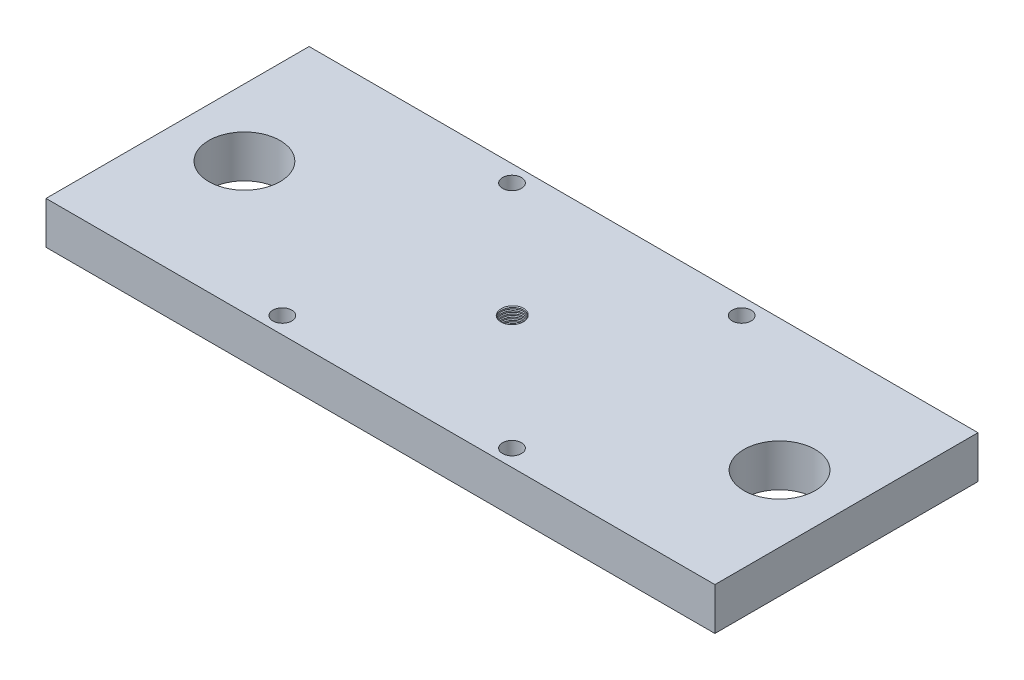
SolidWorks part; units mm, degrees
ref_plane "Front Plane" through (0, 0, 0) normal (0, 0, 1) x (1, 0, 0)
ref_plane "Top Plane" through (0, 0, 0) normal (0, 1, 0) x (1, 0, 0)
ref_plane "Right Plane" through (0, 0, 0) normal (1, 0, 0) x (0, 0, -1)
sketch "Sketch1" plane through (0, 0, 0) normal (0, 1, 0) x (1, 0, 0)
  line L1 (-150, -59) -> (150, -59)
  line L2 (-150, -59) -> (-150, 59)
  line L3 (-150, 59) -> (150, 59)
  line L4 (150, -59) -> (150, 59)
  line L5 (-150, -59) -> (150, 59) construction
  line L6 (-150, 59) -> (150, -59) construction
  circle A0 centre (0, 0) radius 5
  point P1 (0, 0)
  dimension "D3" = 10
  dimension "D1" = 118
  dimension "D2" = 300
extrude "Boss-Extrude1" add sketch "Sketch1" along normal blind 19
sketch "Sketch2" plane through (0, 19, 0) normal (0, 1, 0) x (1, 0, 0)
  circle A0 centre (0, 0) radius 5
  dimension "D1" = 10
sketch "Sketch4" plane through (0, 19, 0) normal (0, 1, 0) x (1, 0, 0)
  line L0 (-150, 59) -> (-150, -59) construction
  line L1 (150, -59) -> (150, 59) construction
  circle A0 centre (-120, 0) radius 16
  circle A1 centre (120, 0) radius 16
  dimension "D3" = 32
  dimension "D1" = 30
  dimension "D2" = 30
extrude "Cut-Extrude1" cut sketch "Sketch4" against normal through all
sketch "Sketch6" plane through (0, 0, 0) normal (0, 1, 0) x (1, 0, 0)
  line L0 (-150, 59) -> (-150, -59) construction
  line L1 (-145.4112, 0) -> (187.1629, 0) construction
  circle A0 centre (-51.5, 51.5) radius 4.25
  circle A1 centre (51.5, 51.5) radius 4.25
  circle A2 centre (51.5, -51.5) radius 4.25
  circle A3 centre (-51.5, -51.5) radius 4.25
  point P16 (0, 0)
  dimension "D1" = 8.5
  dimension "D2" = 51.5
  dimension "D3" = 98.5
  dimension "D4" = 4
extrude "Cut-Extrude11" cut sketch "Sketch6" along direction (0, -1, 0) on the side against the normal blind 9 and the other way blind 19
sketch "Sketch7" plane through (0, 0, 0) normal (0, 1, 0) x (1, 0, 0)
  circle A0 centre (0, 0) radius 5
  circle A1 centre (0, 0) radius 5 construction
curve "Helix/Spiral1" pitch 1.25 height 20.3125 turns 16.25
sketch "Sketch8" plane through (0, 0, 0) normal (1, 0, 0) x (0, 0, -1)
  line L0 (5, 20.625) -> (5, 20)
  line L1 (5, 20) -> (5.5, 20.3125)
  line L2 (5.5, 20.3125) -> (5, 20.625)
  spline S1 degree 3 poles (0, 0) (0.6503, 0.0259) (1.9651, 0.0782) (3.6271, 0.1562) (4.7398, 0.2344) (5.1301, 0.3125) (4.7397, 0.3906) (3.6276, 0.4687) (1.9632, 0.5469) (0, 0.625) (-1.9632, 0.7031) (-3.6276, 0.7812) (-4.7397, 0.8594) (-5.1302, 0.9375) (-4.7397, 1.0156) (-3.6276, 1.0937) (-1.9632, 1.1719) (0, 1.25) (1.9632, 1.3281) (3.6276, 1.4062) (4.7397, 1.4844) (5.1302, 1.5625) (4.7397, 1.6406) (3.6276, 1.7188) (1.9632, 1.7969) (0, 1.875) (-1.9632, 1.9531) (-3.6276, 2.0313) (-4.7397, 2.1094) (-5.1302, 2.1875) (-4.7397, 2.2656) (-3.6276, 2.3438) (-1.9632, 2.4219) (0, 2.5) (1.9632, 2.5781) (3.6276, 2.6563) (4.7397, 2.7344) (5.1302, 2.8125) (4.7397, 2.8906) (3.6276, 2.9688) (1.9632, 3.0469) (0, 3.125) (-1.9632, 3.2031) (-3.6276, 3.2813) (-4.7397, 3.3594) (-5.1302, 3.4375) (-4.7397, 3.5156) (-3.6276, 3.5938) (-1.9632, 3.6719) (0, 3.75) (1.9632, 3.8281) (3.6276, 3.9063) (4.7397, 3.9844) (5.1302, 4.0625) (4.7397, 4.1406) (3.6276, 4.2188) (1.9632, 4.2969) (0, 4.375) (-1.9632, 4.4531) (-3.6276, 4.5313) (-4.7397, 4.6094) (-5.1302, 4.6875) (-4.7397, 4.7656) (-3.6276, 4.8438) (-1.9632, 4.9219) (0, 5) (1.9632, 5.0781) (3.6276, 5.1563) (4.7397, 5.2344) (5.1302, 5.3125) (4.7397, 5.3906) (3.6276, 5.4688) (1.9632, 5.5469) (0, 5.625) (-1.9632, 5.7031) (-3.6276, 5.7813) (-4.7397, 5.8594) (-5.1302, 5.9375) (-4.7397, 6.0156) (-3.6276, 6.0938) (-1.9632, 6.1719) (0, 6.25) (1.9632, 6.3281) (3.6276, 6.4063) (4.7397, 6.4844) (5.1302, 6.5625) (4.7397, 6.6406) (3.6276, 6.7188) (1.9632, 6.7969) (0, 6.875) (-1.9632, 6.9531) (-3.6276, 7.0313) (-4.7397, 7.1094) (-5.1302, 7.1875) (-4.7397, 7.2656) (-3.6276, 7.3438) (-1.9632, 7.4219) (0, 7.5) (1.9632, 7.5781) (3.6276, 7.6563) (4.7397, 7.7344) (5.1302, 7.8125) (4.7397, 7.8906) (3.6276, 7.9688) (1.9632, 8.0469) (0, 8.125) (-1.9632, 8.2031) (-3.6276, 8.2813) (-4.7397, 8.3594) (-5.1302, 8.4375) (-4.7397, 8.5156) (-3.6276, 8.5938) (-1.9632, 8.6719) (0, 8.75) (1.9632, 8.8281) (3.6276, 8.9063) (4.7397, 8.9844) (5.1302, 9.0625) (4.7397, 9.1406) (3.6276, 9.2188) (1.9632, 9.2969) (0, 9.375) (-1.9632, 9.4531) (-3.6276, 9.5313) (-4.7397, 9.6094) (-5.1302, 9.6875) (-4.7397, 9.7656) (-3.6276, 9.8438) (-1.9632, 9.9219) (0, 10) (1.9632, 10.0781) (3.6276, 10.1563) (4.7397, 10.2344) (5.1302, 10.3125) (4.7397, 10.3906) (3.6276, 10.4688) (1.9632, 10.5469) (0, 10.625) (-1.9632, 10.7031) (-3.6276, 10.7813) (-4.7397, 10.8594) (-5.1302, 10.9375) (-4.7397, 11.0156) (-3.6276, 11.0938) (-1.9632, 11.1719) (0, 11.25) (1.9632, 11.3281) (3.6276, 11.4063) (4.7397, 11.4844) (5.1302, 11.5625) (4.7397, 11.6406) (3.6276, 11.7188) (1.9632, 11.7969) (0, 11.875) (-1.9632, 11.9531) (-3.6276, 12.0313) (-4.7397, 12.1094) (-5.1302, 12.1875) (-4.7397, 12.2656) (-3.6276, 12.3438) (-1.9632, 12.4219) (0, 12.5) (1.9632, 12.5781) (3.6276, 12.6563) (4.7397, 12.7344) (5.1302, 12.8125) (4.7397, 12.8906) (3.6276, 12.9688) (1.9632, 13.0469) (0, 13.125) (-1.9632, 13.2031) (-3.6276, 13.2813) (-4.7397, 13.3594) (-5.1302, 13.4375) (-4.7397, 13.5156) (-3.6276, 13.5938) (-1.9632, 13.6719) (0, 13.75) (1.9632, 13.8281) (3.6276, 13.9063) (4.7397, 13.9844) (5.1302, 14.0625) (4.7397, 14.1406) (3.6276, 14.2188) (1.9632, 14.2969) (0, 14.375) (-1.9632, 14.4531) (-3.6276, 14.5313) (-4.7397, 14.6094) (-5.1302, 14.6875) (-4.7397, 14.7656) (-3.6276, 14.8438) (-1.9632, 14.9219) (0, 15) (1.9632, 15.0781) (3.6276, 15.1563) (4.7397, 15.2344) (5.1302, 15.3125) (4.7397, 15.3906) (3.6276, 15.4688) (1.9632, 15.5469) (0, 15.625) (-1.9632, 15.7031) (-3.6276, 15.7813) (-4.7397, 15.8594) (-5.1302, 15.9375) (-4.7397, 16.0156) (-3.6276, 16.0938) (-1.9632, 16.1719) (0, 16.25) (1.9632, 16.3281) (3.6276, 16.4062) (4.7397, 16.4844) (5.1302, 16.5625) (4.7397, 16.6406) (3.6276, 16.7187) (1.9632, 16.7969) (0, 16.875) (-1.9632, 16.9531) (-3.6276, 17.0312) (-4.7397, 17.1094) (-5.1302, 17.1875) (-4.7397, 17.2656) (-3.6276, 17.3437) (-1.9632, 17.4219) (0, 17.5) (1.9632, 17.5781) (3.6276, 17.6562) (4.7397, 17.7344) (5.1302, 17.8125) (4.7397, 17.8906) (3.6276, 17.9687) (1.9632, 18.0469) (0, 18.125) (-1.9632, 18.2031) (-3.6276, 18.2812) (-4.7397, 18.3594) (-5.1302, 18.4375) (-4.7397, 18.5156) (-3.6276, 18.5937) (-1.9632, 18.6719) (0, 18.75) (1.9632, 18.8281) (3.6276, 18.9062) (4.7397, 18.9844) (5.1302, 19.0625) (4.7397, 19.1406) (3.6276, 19.2188) (1.9632, 19.2969) (0, 19.375) (-1.9632, 19.4531) (-3.6276, 19.5313) (-4.7397, 19.6094) (-5.1302, 19.6875) (-4.7397, 19.7656) (-3.6276, 19.8438) (-1.9632, 19.9219) (0, 20) (1.9632, 20.0781) (3.6276, 20.1563) (4.7397, 20.2343) (5, 20.2866) (5, 20.3125) knots 0 0 0 0 0.003846 0.007692 0.011538 0.015385 0.019231 0.023077 0.026923 0.030769 0.034615 0.038462 0.042308 0.046154 0.05 0.053846 0.057692 0.061538 0.065385 0.069231 0.073077 0.076923 0.080769 0.084615 0.088462 0.092308 0.096154 0.1 0.103846 0.107692 0.111538 0.115385 0.119231 0.123077 0.126923 0.130769 0.134615 0.138462 0.142308 0.146154 0.15 0.153846 0.157692 0.161538 0.165385 0.169231 0.173077 0.176923 0.180769 0.184615 0.188462 0.192308 0.196154 0.2 0.203846 0.207692 0.211538 0.215385 0.219231 0.223077 0.226923 0.230769 0.234615 0.238462 0.242308 0.246154 0.25 0.253846 0.257692 0.261538 0.265385 0.269231 0.273077 0.276923 0.280769 0.284615 0.288462 0.292308 0.296154 0.3 0.303846 0.307692 0.311538 0.315385 0.319231 0.323077 0.326923 0.330769 0.334615 0.338462 0.342308 0.346154 0.35 0.353846 0.357692 0.361538 0.365385 0.369231 0.373077 0.376923 0.380769 0.384615 0.388462 0.392308 0.396154 0.4 0.403846 0.407692 0.411538 0.415385 0.419231 0.423077 0.426923 0.430769 0.434615 0.438462 0.442308 0.446154 0.45 0.453846 0.457692 0.461538 0.465385 0.469231 0.473077 0.476923 0.480769 0.484615 0.488462 0.492308 0.496154 0.5 0.503846 0.507692 0.511538 0.515385 0.519231 0.523077 0.526923 0.530769 0.534615 0.538462 0.542308 0.546154 0.55 0.553846 0.557692 0.561538 0.565385 0.569231 0.573077 0.576923 0.580769 0.584615 0.588462 0.592308 0.596154 0.6 0.603846 0.607692 0.611538 0.615385 0.619231 0.623077 0.626923 0.630769 0.634615 0.638462 0.642308 0.646154 0.65 0.653846 0.657692 0.661538 0.665385 0.669231 0.673077 0.676923 0.680769 0.684615 0.688462 0.692308 0.696154 0.7 0.703846 0.707692 0.711538 0.715385 0.719231 0.723077 0.726923 0.730769 0.734615 0.738462 0.742308 0.746154 0.75 0.753846 0.757692 0.761538 0.765385 0.769231 0.773077 0.776923 0.780769 0.784615 0.788462 0.792308 0.796154 0.8 0.803846 0.807692 0.811538 0.815385 0.819231 0.823077 0.826923 0.830769 0.834615 0.838462 0.842308 0.846154 0.85 0.853846 0.857692 0.861538 0.865385 0.869231 0.873077 0.876923 0.880769 0.884615 0.888462 0.892308 0.896154 0.9 0.903846 0.907692 0.911538 0.915385 0.919231 0.923077 0.926923 0.930769 0.934615 0.938462 0.942308 0.946154 0.95 0.953846 0.957692 0.961538 0.965385 0.969231 0.973077 0.976923 0.980769 0.984615 0.988462 0.992308 0.996154 1 1 1 1 construction
  point P5 (5, 20.3125)
  dimension "D1" = 0.5
  dimension "D2" = 0.625
sweep "Cut-Sweep1" cut profiles "Sketch8" path "Helix/Spiral1" align with end faces yes
